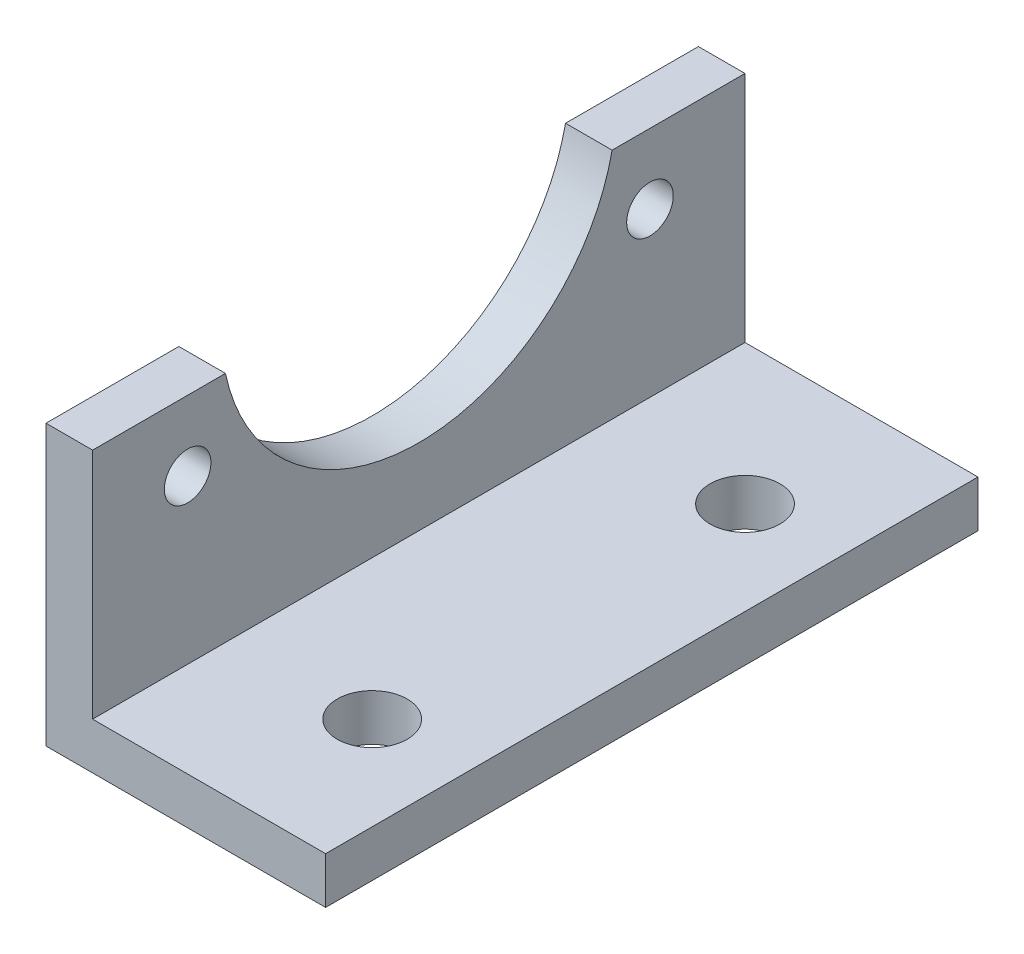
SolidWorks part; units mm, degrees
ref_plane "Front Plane" through (0, 0, 0) normal (0, 0, 1) x (1, 0, 0)
ref_plane "Top Plane" through (0, 0, 0) normal (0, 1, 0) x (1, 0, 0)
ref_plane "Right Plane" through (0, 0, 0) normal (1, 0, 0) x (0, 0, -1)
sketch "Sketch1" plane through (0, 0, 0) normal (0, 0, 1) x (1, 0, 0)
  line L0 (0, 0) -> (0, 38.1)
  line L1 (0, 38.1) -> (6.35, 38.1)
  line L2 (6.35, 38.1) -> (6.35, 6.35)
  line L3 (0, 0) -> (6.35, 6.35) construction
  line L4 (38.1, 6.35) -> (6.35, 6.35)
  line L5 (38.1, 0) -> (38.1, 6.35)
  line L6 (0, 0) -> (38.1, 0)
  dimension "D1" = 38.1
  dimension "D2" = 6.35
  dimension "D3" = 45
extrude "Boss-Extrude1" add sketch "Sketch1" along normal blind 88.9
sketch "Sketch2" plane through (0, 0, 0) normal (-1, 0, 0) x (0, 0, 1)
  line L0 (70.795, 38.1) -> (88.9, 38.1)
  line L1 (88.9, 38.1) -> (88.9, 0)
  line L2 (88.9, 0) -> (0, 0)
  line L3 (44.45, 0) -> (44.45, 16.7333) construction
  line L5 (0, 38.1) -> (0, 0)
  line L6 (18.105, 38.1) -> (0, 38.1)
  line L7 (18.105, 38.1) -> (70.795, 38.1)
  circle A0 centre (75.95, 28.575) radius 3.175
  circle A1 centre (12.95, 28.575) radius 3.175
  arc A3 (70.795, 38.1) -> (18.105, 38.1) centre (44.45, 43.6583) cw
  point P19 (75.95, 28.575)
  line M18 (88.9, 38.1) -> (0, 38.1)
  dimension "D1" = 6.35
  dimension "D2" = 38.1
  dimension "D5" = 26.925
  dimension "D3" = 44.45
  dimension "D4" = 9.525
  dimension "D6" = 88.9
extrude "Cut-Extrude1" cut sketch "Sketch2" against normal blind 76.2 contours A1 | A0 | A3 M18 region at (0, 29.1736, 44.45) region at (0, 28.575, 75.95) region at (0, 28.575, 12.95)
sketch "Sketch3" plane through (0, 0, 0) normal (0, -1, 0) x (1, 0, 0)
  line L0 (0, 44.45) -> (25.4, 44.45) construction
  line L1 (0, 88.9) -> (0, 0) construction
  line L2 (25.4, 44.45) -> (25.4, 69.85) construction
  circle A0 centre (25.4, 69.85) radius 4.7625
  circle A1 centre (25.4, 19.05) radius 4.7625
  dimension "D3" = 9.525
  dimension "D1" = 25.4
  dimension "D2" = 25.4
extrude "Cut-Extrude2" cut sketch "Sketch3" against normal through all
